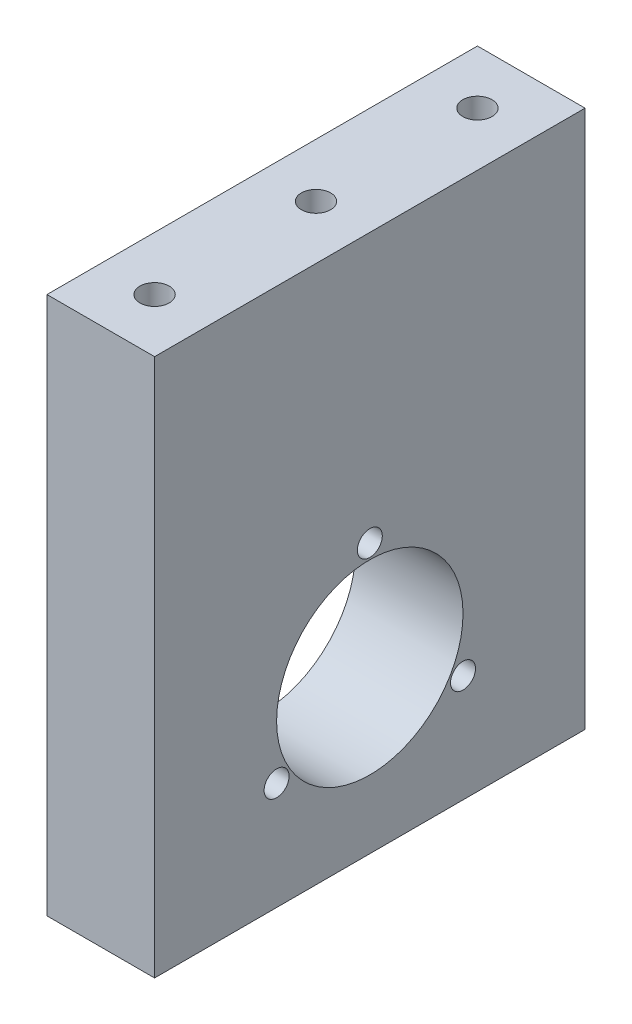
SolidWorks part; units mm, degrees
ref_plane "Front Plane" through (0, 0, 0) normal (0, 0, 1) x (1, 0, 0)
ref_plane "Top Plane" through (0, 0, 0) normal (0, 1, 0) x (1, 0, 0)
ref_plane "Right Plane" through (0, 0, 0) normal (1, 0, 0) x (0, 0, -1)
sketch "Sketch1" plane through (0, 0, 0) normal (1, 0, 0) x (0, 0, -1)
  line L1 (-25.4, -31.75) -> (25.4, -31.75)
  line L2 (-25.4, -31.75) -> (-25.4, 31.75)
  line L3 (-25.4, 31.75) -> (25.4, 31.75)
  line L4 (25.4, -31.75) -> (25.4, 31.75)
  line L5 (-25.4, -31.75) -> (25.4, 31.75) construction
  line L6 (-25.4, 31.75) -> (25.4, -31.75) construction
  point P0 (0, 0)
  dimension "D1" = 50.8
  dimension "D2" = 63.5
extrude "Boss-Extrude1" add sketch "Sketch1" along normal blind 12.7
hole_wizard "Ø22.0 (22) Diameter Hole1" positions "Sketch3" profile "Sketch2" hole size "Ø22.0" standard "ANSI Metric" end condition through all
sketch "Sketch3" plane through (12.7, 0, 0) normal (1, 0, 0) x (0, 0, -1)
  line L1 (25.4, 31.75) -> (-25.4, 31.75) construction
  line L2 (0, -31.75) -> (0, 31.75) construction
  line L3 (-25.4, -31.75) -> (25.4, -31.75) construction
  point P0 (0, -12.7)
  dimension "D1" = 44.45
sketch "Sketch2" plane through (12.7, -12.7, 0) normal (0, 1, 0) x (0, 0, -1)
  line L0 (0, 0) -> (0, 12.7)
  line L1 (0, 12.7) -> (11, 12.7)
  line L2 (11, 12.7) -> (11, 0)
  line L5 (11, 0) -> (0, 0)
  line L11 (0, -6.35) -> (0, 107.95) construction
  dimension "Thru Hole Dia." = 22
  dimension "Thru Hole Depth" = 12.7
hole_wizard "#8-32 Tapped Hole1" positions "Sketch12" profile "Sketch11" tap size "#8-32" standard "ANSI Inch"
sketch "Sketch12" plane through (0, 31.75, 0) normal (0, 1, 0) x (1, 0, 0)
  line L0 (6.35, 25.4) -> (6.35, -25.4) construction
  line L1 (12.7, 25.4) -> (0, 25.4) construction
  line L2 (12.7, -25.4) -> (0, -25.4) construction
  line L3 (12.7, 0) -> (0, 0) construction
  line L4 (12.7, 25.4) -> (12.7, -25.4) construction
  line L5 (0, 25.4) -> (0, -25.4) construction
  point P0 (6.35, 19.05)
  point P2 (6.35, -19.05)
  point P13 (6.35, 0)
  dimension "D1" = 6.35
  dimension "D2" = 6.35
sketch "Sketch11" plane through (6.35, 31.75, -19.05) normal (1, 0, 0) x (0, 0, 1)
  line L0 (0, 0) -> (0, 11.7058)
  line L1 (0, 11.7058) -> (1.7272, 10.668)
  line L2 (1.7272, 10.668) -> (1.7272, 0)
  line L5 (1.7272, 0) -> (0, 0)
  line L10 (0, 11.7058) -> (-1.7272, 10.668) construction
  line L11 (0, -6.35) -> (0, 107.95) construction
  dimension "Tap Drill Dia." = 3.4544
  dimension "Tap Drill Depth" = 10.668
  dimension "Drill Angle" = 118
hole_wizard "#4 Clearance Hole1" positions "Sketch14" profile "Sketch13" hole size "#4" standard "ANSI Inch" end condition through all
sketch "Sketch14" plane through (0, 0, 0) normal (-1, 0, 0) x (0, 0, 1)
  line L0 (0, 31.75) -> (0, -31.75) construction
  line L1 (-25.4, 31.75) -> (25.4, 31.75) construction
  line L2 (25.4, -31.75) -> (-25.4, -31.75) construction
  circle A0 centre (0, -12.7) radius 11 construction
  point P0 (0, 0)
  dimension "D1" = 12.7
sketch "Sketch13" plane through (0, 0, 0) normal (0, 1, 0) x (0, 0, 1)
  line L0 (0, 0) -> (0, 12.7)
  line L1 (0, 12.7) -> (1.4732, 12.7)
  line L2 (1.4732, 12.7) -> (1.4732, 0)
  line L5 (1.4732, 0) -> (0, 0)
  line L11 (0, -6.35) -> (0, 107.95) construction
  dimension "Thru Hole Dia." = 2.9464
  dimension "Thru Hole Depth" = 12.7
pattern_circular "CirPattern1" count 3 over 360 about axis through (0, -12.7, 0) along (1, 0, 0) of "#4 Clearance Hole1"
